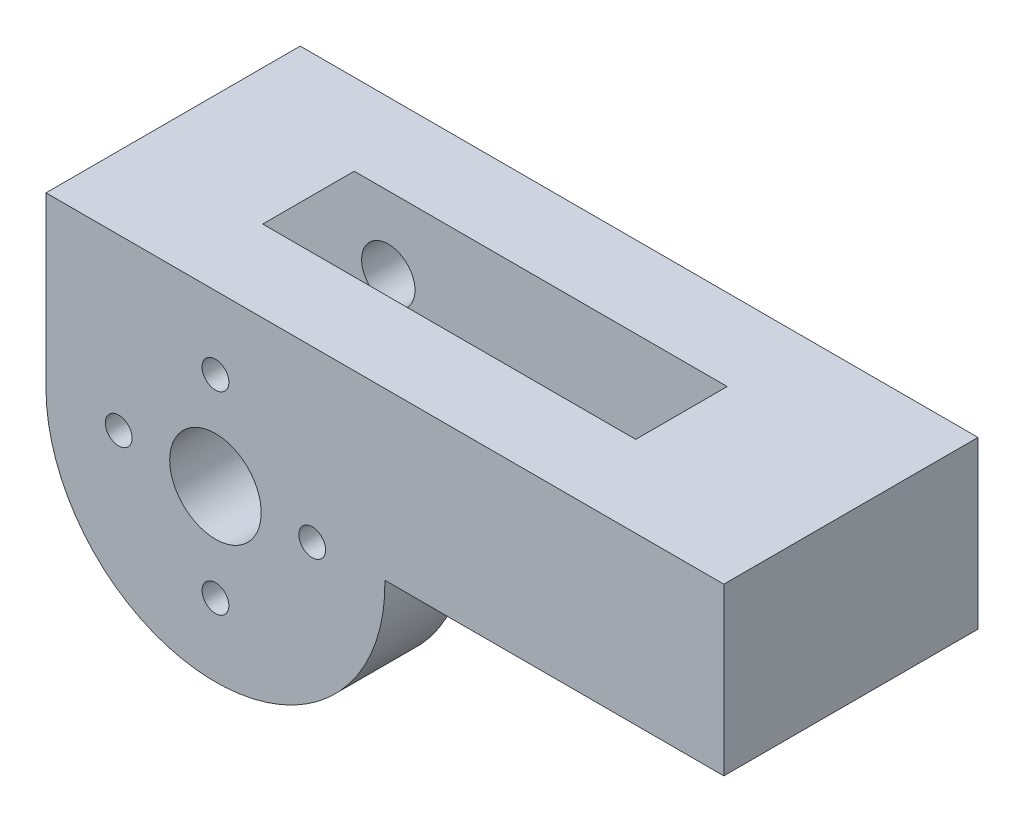
SolidWorks part; units mm, degrees
ref_plane "Front Plane" through (0, 0, 0) normal (0, 0, 1) x (1, 0, 0)
ref_plane "Top Plane" through (0, 0, 0) normal (0, 1, 0) x (1, 0, 0)
ref_plane "Right Plane" through (0, 0, 0) normal (1, 0, 0) x (0, 0, -1)
sketch "Sketch1" plane through (0, 0, 0) normal (0, 0, 1) x (1, 0, 0)
  line L0 (-12.7, 0) -> (-12.7, 12.7)
  line L5 (-12.7, 12.7) -> (38.1, 12.7)
  line L6 (38.1, 12.7) -> (38.1, 0.254)
  line L7 (38.1, 0.254) -> (12.6975, 0.254)
  arc A1 (-12.7, 0) -> (12.6975, 0.254) centre (0, 0) ccw
  circle A2 centre (0, 0) radius 3.429
  dimension "D3" = 6.858
  dimension "D1" = 12.7
  dimension "D2" = 0.254
  dimension "D4" = 38.1
  dimension "D5" = 12.7
extrude "Boss-Extrude1" add sketch "Sketch1" along normal mid plane 19.05
sketch "Sketch3" plane through (0, 0, 9.525) normal (0, 0, 1) x (1, 0, 0)
  line L2 (25.4, 12.7) -> (25.4, 0.254)
  line L3 (12.6975, 0.254) -> (38.1, 0.254) construction
  line L6 (25.4, 0.254) -> (12.9515, 0.254)
  line L14 (38.1, 0.254) -> (38.1, 12.7) construction
  line L16 (0, 12.954) -> (0, 12.7)
  line L17 (38.1, 12.7) -> (-12.7, 12.7) construction
  line L18 (0, 12.7) -> (25.4, 12.7)
  arc A2 (0, 12.954) -> (12.9515, 0.254) centre (0, 0) ccw
  dimension "D1" = 12.7
  dimension "D2" = 25.908
extrude "Cut-Extrude1" cut sketch "Sketch3" against normal mid plane 6.858 from surface starting at plane "Front Plane"
sketch "Sketch4" plane through (0, 0, 9.525) normal (0, 0, 1) x (1, 0, 0)
  circle A0 centre (7.25, 0) radius 1.004
  circle A1 centre (0, -7.25) radius 1.004
  circle A2 centre (-7.25, 0) radius 1.004
  circle A3 centre (0, 7.25) radius 1.004
  point P12 (0, 0)
  dimension "D3" = 2.008
  dimension "D1" = 7.25
  dimension "D2" = 4
extrude "Cut-Extrude2" cut sketch "Sketch4" against normal through all
sketch "Sketch5" plane through (0, 0, -9.525) normal (0, 0, -1) x (-1, 0, 0)
  circle A0 centre (7.25, 0) radius 2
  circle A1 centre (0, -7.25) radius 2
  circle A2 centre (-7.25, 0) radius 2
  circle A3 centre (0, 7.25) radius 2
  point P12 (0, 0)
  dimension "D2" = 4
  dimension "D1" = 4
extrude "Cut-Extrude3" cut sketch "Sketch5" against normal offset from surface (14.954 mm away) 2 up to face at (8.254, 0, 3.429) offset beyond the face yes
equation "\"tightTol\"= 0.005in"
equation "\"normTol\"= 0.01in"
equation "\"looseTol\"= 0.02in"
equation "\"D2@Sketch1\"=\"normTol\""
equation "\"D3@Sketch1\"=0.25+\"looseTol\""
equation "\"D1@Cut-Extrude1\"=\"looseTol\"+0.250000in"
equation "\"D2@Sketch3\"=1+\"looseTol\""
equation "\"D1@Sketch4\"=7.25mm"
equation "\"D3@Sketch4\"=1.5mm+\"looseTol\""
equation "\"D1@Sketch5\"=4mm"
equation "\"D1@Cut-Extrude3\"=2mm"
